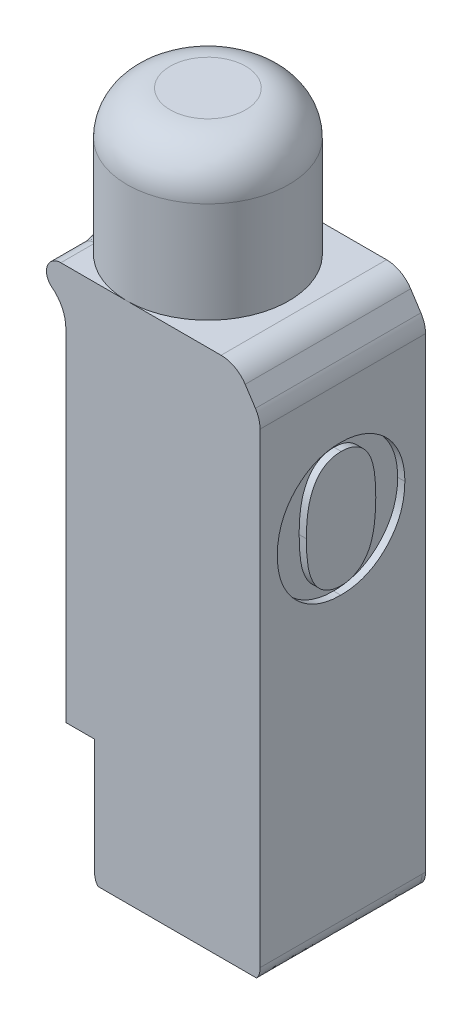
SolidWorks part; units mm, degrees
ref_plane "Přední rovina" through (0, 0, 0) normal (0, 0, 1) x (1, 0, 0)
ref_plane "Horní rovina" through (0, 0, 0) normal (0, 1, 0) x (1, 0, 0)
ref_plane "Pravá rovina" through (0, 0, 0) normal (1, 0, 0) x (0, 0, -1)
sketch "Skica1" plane through (0, 0, 0) normal (0, 0, 1) x (1, 0, 0)
  line L0 (-224.5983, 0) -> (11005.3146, 0) construction
  line L1 (0, -224.5983) -> (0, 11005.3146) construction
  line L3 (-2.3, 0) -> (2.3, 0) construction
  line L4 (-2.3, 0) -> (-2.3, -3.6)
  line L5 (-2.3, -3.6) -> (2.3, -3.6)
  line L6 (2.3, 0) -> (2.3, -3.6)
  line L7 (-2.3, 0) -> (2.3, -3.6) construction
  line L8 (-2.3, -3.6) -> (2.3, 0) construction
  line L9 (-2.3, 10) -> (2.3, 10) construction
  line L10 (-2.3, 10) -> (-2.3, 0) construction
  line L11 (-2.3, 0) -> (2.3, 0) construction
  line L12 (2.3, 10) -> (2.3, 0)
  line L13 (-2.3, 10) -> (2.3, 0) construction
  line L14 (-2.3, 0) -> (2.3, 10) construction
  line L17 (-3.65, 15) -> (0.85, 15)
  line L18 (-3.65, 15) -> (-3.65, 11)
  line L19 (-3.65, 11) -> (0.85, 11) construction
  line L20 (0.85, 15) -> (0.85, 11)
  line L21 (-3.65, 15) -> (0.85, 11) construction
  line L22 (-3.65, 11) -> (0.85, 15) construction
  line L24 (-1.4, -992.1425) -> (-1.4, 49007.8575) construction
  line L25 (-2.3, 10) -> (-3.1, 10) construction
  line L27 (-2.3, 10) -> (-2.3, 0) construction
  line L28 (-2.3, 0) -> (-3.1, 0)
  line L29 (-3.1, 10) -> (-3.1, 0)
  line L30 (-3.1, 10) -> (-4.45, 11)
  line L31 (-4.45, 11) -> (-3.65, 11)
  line L32 (2.3, 10) -> (1.65, 11)
  line L33 (1.65, 11) -> (0.85, 11)
  point P4 (0, -1.8)
  point P10 (-1.4, 13)
  point P12 (0, 5)
  dimension "D1" = 3.6
  dimension "D2" = 4.6
  dimension "D3" = 4.6
  dimension "D4" = 10
  dimension "D5" = 4.5
  dimension "D6" = 4
  dimension "D7" = 1.4
  dimension "D8" = 0.8
  dimension "D9" = 1
  dimension "D10" = 0.8
extrude "Přidat vysunutím1" add sketch "Skica1" along normal blind 4.6
sketch "Skica2" plane through (0, 0, 4.6) normal (0, 0, 1) x (1, 0, 0)
  line L1 (2.3, 10) -> (1.65, 11) construction
  line L2 (1.65, 11) -> (0.85, 11) construction
  line L4 (-3.1, 10) -> (-3.1, 0) construction
  line L10 (-3.1, 10) -> (-3.1, 0)
  line L13 (-3.1, 0) -> (2.3, 0)
  line L14 (-3.65, 11) -> (-4.45, 11) construction
  line L15 (-4.45, 11) -> (-3.1, 10) construction
  line L16 (2.3, 10) -> (1.65, 11)
  line L17 (1.65, 11) -> (0.85, 11)
  line L18 (-3.65, 11) -> (-4.45, 11)
  line L19 (-4.45, 11) -> (-3.1, 10)
  line L20 (-3.65, 11) -> (0.85, 11)
  line L21 (2.3, 0) -> (2.3, 10)
extrude "Přidat vysunutím2" add sketch "Skica2" along normal blind 0.8
sketch "Skica4" plane through (0, 15, 0) normal (0, 1, 0) x (1, 0, 0)
  line L0 (-1002.2, -2.25) -> (48997.8, -2.25) construction
  line L2 (-1.4, -1000) -> (-1.4, 49000) construction
  line L3 (0.85, -4.6) -> (-3.65, -4.6) construction
  line L4 (0.85, -4.6) -> (0.85, 0) construction
  line L5 (0.85, 0) -> (-3.65, 0) construction
  line L6 (-3.65, -4.6) -> (-3.65, 0) construction
  line L7 (0.85, -4.6) -> (-3.65, -4.6)
  line L8 (0.85, -4.6) -> (0.85, 0)
  line L9 (0.85, 0) -> (-3.65, 0)
  line L10 (-3.65, -4.6) -> (-3.65, 0)
  line L11 (0, -1000) -> (0, 49000) construction
  circle A0 centre (-1.4, -2.25) radius 2.25
  line M1 (0.85, 0) -> (-3.65, 0)
  line M2 (-3.65, 0) -> (-3.65, -4.6)
  line M3 (-3.65, -4.6) -> (0.85, -4.6)
  line M4 (0.85, -4.6) -> (0.85, 0)
  dimension "D1" = 4.5
  dimension "D2" = 1.4
extrude "Odebrat vysunutím1" cut sketch "Skica4" against normal up to surface (4 mm away) contours A0 M2 M3 M4 | A0 M4 M1 M2 | A0 M4 M1 region at (-1.4, 15, 4.5492) region at (0.3474, 15, 0.5026) region at (-3.1474, 15, 0.5026) up to face at (-1.4, 11, 2.5)
fillet "Zaoblit4" radius 0.4 3 edges at (-2.3, -3.6, 2.3) (0, -3.6, 4.6) (2.3, -3.6, 2.3) conic rho 0.5
fillet "Zaoblit5" radius 1.2 1 edges at (-1.4, 15, 4.5)
fillet "Zaoblit6" radius 1 1 edges at (-3.1, 10, 2.7)
fillet "Zaoblit7" radius 0.4 1 edges at (-4.45, 11, 2.7)
fillet "Zaoblit8" radius 0.8 2 edges at (1.65, 11, 2.7) (2.3, 10, 2.7)
sketch "Skica5" plane through (0, 0, 0) normal (0, 0, -1) x (-1, 0, 0)
  line L0 (2.3, 0) -> (-2.3, 0)
  line L1 (-2.3, -3.2) -> (-2.3, 9.7628) construction
  line L2 (-2.3, 0) -> (-2.3, 9.7628)
  line L8 (1.4, 11) -> (-1.2159, 11)
  line L9 (-1.8866, 10.636) -> (-2.1708, 10.1988)
  line L10 (-2.3, 9.7628) -> (-2.3, -3.2)
  line L11 (-1.9, -3.6) -> (1.9, -3.6)
  line L12 (2.3, -3.2) -> (2.3, 0)
  line L13 (2.3, 0) -> (3.1, 0)
  line L14 (3.1, 0) -> (3.1, 9.4963)
  line L15 (3.2387, 11) -> (1.4, 11)
  line L16 (1.4, 11) -> (-1.2159, 11)
  line L17 (-1.8866, 10.636) -> (-2.1708, 10.1988)
  line L21 (2.3, 0) -> (3.1, 0)
  line L22 (3.1, 0) -> (3.1, 9.4963)
  line L23 (3.2387, 11) -> (1.4, 11)
  arc A4 (-1.2159, 11) -> (-1.8866, 10.636) centre (-1.2159, 10.2) ccw
  arc A5 (-2.1708, 10.1988) -> (-2.3, 9.7628) centre (-1.5, 9.7628) ccw
  arc A6 (3.4848, 10.2846) -> (3.1, 9.4963) centre (4.1, 9.4963) ccw
  arc A7 (3.4848, 10.2846) -> (3.2387, 11) centre (3.2387, 10.6) ccw
  arc A8 (-1.2159, 11) -> (-1.8866, 10.636) centre (-1.2159, 10.2) ccw
  arc A9 (-2.1708, 10.1988) -> (-2.3, 9.7628) centre (-1.5, 9.7628) ccw
  arc A10 (3.4848, 10.2846) -> (3.1, 9.4963) centre (4.1, 9.4963) ccw
  arc A11 (3.4848, 10.2846) -> (3.2387, 11) centre (3.2387, 10.6) ccw
  parabola Q2 (-2.3, -3.2) -> (-1.9, -3.6) focus (-2.1, -3.4) apex (-2.2, -3.5)
  parabola Q3 (1.9, -3.6) -> (2.3, -3.2) focus (2.1, -3.4) apex (2.2, -3.5)
  dimension "D1" = 0
extrude "Přidat vysunutím3" add sketch "Skica5" along normal blind 0.8
sketch "Skica7" plane through (0, 11, 0) normal (0, 1, 0) x (1, 0, 0)
  line L0 (-1001.2237, -4.5) -> (48998.7763, -4.5) construction
  line L1 (-3.6387, -3.5468) -> (-3.6387, -5.4) construction
  line L2 (2.3, -5.4) -> (-3.6387, -5.4)
  line L3 (2.3, -5.4) -> (2.3, -4.5)
  line L4 (2.3, -4.5) -> (-3.6387, -4.5)
  line L5 (-3.6387, -5.4) -> (-3.6387, -4.5)
  line L6 (-1001.1851, 0) -> (48998.8149, 0) construction
  line L7 (-3.6387, 0.8) -> (-3.6387, -0.9532) construction
  line L8 (-3.6387, 0.8) -> (-3.6387, 0)
  line L10 (-3.6387, 0.8) -> (2.3, 0.8)
  line L11 (2.3, 0.8) -> (2.3, 0)
  line L12 (-3.6387, 0) -> (2.3, 0)
  arc A0 (-3.2387, -3.5468) -> (-3.2387, -0.9532) centre (-1.4, -2.25) ccw construction
  point P5 (0, 0)
extrude "Odebrat vysunutím3" cut sketch "Skica7" against normal through all
sketch "Skica8" plane through (0, 0, 0) normal (0, 0, -1) x (-1, 0, 0)
  line L4 (2.3, 0) -> (3.1, 0)
  line L5 (-2.3, 9.7628) -> (-2.3, -3.2)
  line L6 (-1.9, -3.6) -> (1.9, -3.6)
  line L7 (2.3, -3.2) -> (2.3, 0)
  line L8 (2.3, 0) -> (3.1, 0)
  line L9 (-2.3, 9.7628) -> (-2.3, -3.2)
  line L10 (-1.9, -3.6) -> (1.9, -3.6)
  line L11 (2.3, -3.2) -> (2.3, 0)
  line L16 (3.1, 0) -> (3.1, 9.4963)
  line L17 (3.1, 0) -> (3.1, 9.4963)
  line L18 (3.2387, 11) -> (1.4, 11)
  line L19 (3.2387, 11) -> (1.4, 11)
  line L20 (1.4, 11) -> (-1.2159, 11)
  line L21 (1.4, 11) -> (-1.2159, 11)
  line L22 (-1.8866, 10.636) -> (-2.1708, 10.1988)
  line L23 (-1.8866, 10.636) -> (-2.1708, 10.1988)
  arc A4 (3.4848, 10.2846) -> (3.1, 9.4963) centre (4.1, 9.4963) ccw
  arc A5 (3.4848, 10.2846) -> (3.1, 9.4963) centre (4.1, 9.4963) ccw
  arc A6 (3.4848, 10.2846) -> (3.2387, 11) centre (3.2387, 10.6) ccw
  arc A7 (3.4848, 10.2846) -> (3.2387, 11) centre (3.2387, 10.6) ccw
  arc A8 (-1.2159, 11) -> (-1.8866, 10.636) centre (-1.2159, 10.2) ccw
  arc A9 (-1.2159, 11) -> (-1.8866, 10.636) centre (-1.2159, 10.2) ccw
  arc A10 (-2.1708, 10.1988) -> (-2.3, 9.7628) centre (-1.5, 9.7628) ccw
  arc A11 (-2.1708, 10.1988) -> (-2.3, 9.7628) centre (-1.5, 9.7628) ccw
  parabola Q2 (-2.3, -3.2) -> (-1.9, -3.6) focus (-2.1, -3.4) apex (-2.2, -3.5)
  parabola Q3 (1.9, -3.6) -> (2.3, -3.2) focus (2.1, -3.4) apex (2.2, -3.5)
  parabola Q4 (-2.3, -3.2) -> (-1.9, -3.6) focus (-2.1, -3.4) apex (-2.2, -3.5)
  parabola Q5 (1.9, -3.6) -> (2.3, -3.2) focus (2.1, -3.4) apex (2.2, -3.5)
  dimension "D1" = 0
extrude "Přidat vysunutím4" add sketch "Skica8" along normal blind 0.1
sketch "Skica9" plane through (-3.1, 0, 3) normal (1, 0, 0) x (0, 0, -1)
  text T0 "I" font "Century Schoolbook" height 3.5
extrude "Odebrat vysunutím4" cut sketch "Skica9" along normal blind 0.2
sketch "Skica11" plane through (2.3, 0, 0) normal (1, 0, 0) x (0, 0, -1)
  text T0 "O" font "Century Schoolbook" height 3.5
extrude "Odebrat vysunutím5" cut sketch "Skica11" against normal blind 0.2
